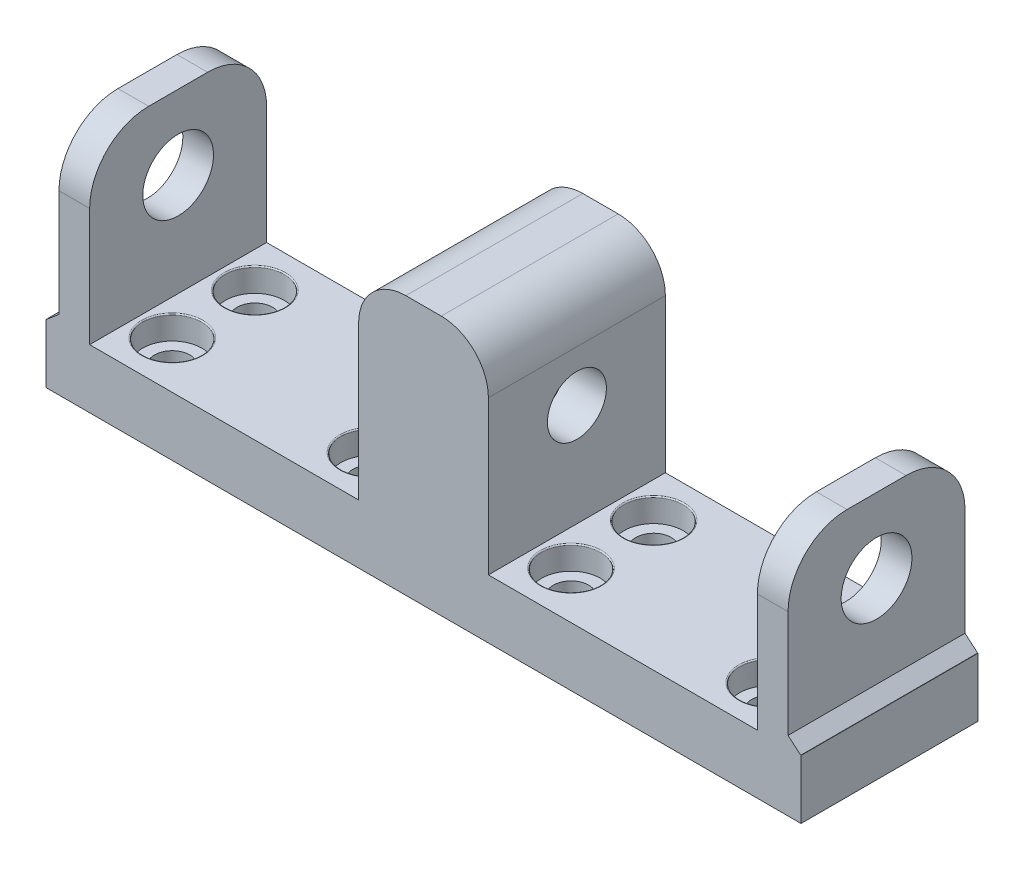
SolidWorks part; units mm, degrees
ref_plane "Alzado" through (0, 0, 0) normal (0, 0, 1) x (1, 0, 0)
ref_plane "Planta" through (0, 0, 0) normal (0, 1, 0) x (1, 0, 0)
ref_plane "Vista lateral" through (0, 0, 0) normal (1, 0, 0) x (0, 0, -1)
sketch "Croquis1" plane through (0, 0, 0) normal (0, 0, 1) x (1, 0, 0)
  line L0 (0, 11) -> (0, -11) construction
  line L1 (-1.5, 11) -> (1.5, 11)
  line L2 (-5.5, 7) -> (-5.5, -6)
  line L3 (-5.5, -11) -> (5.5, -11)
  line L4 (5.5, 7) -> (5.5, -6)
  line L5 (-5.5, 11) -> (5.5, -11) construction
  line L6 (-5.5, -11) -> (5.5, 11) construction
  line L7 (-5.5, -11) -> (-11.5, -11)
  line L9 (-5.5, -6) -> (-11.5, -6)
  line L10 (-11.5, -11) -> (-11.5, -6)
  line L11 (5.5, -6) -> (11.5, -6)
  line L12 (11.5, -11) -> (11.5, -6)
  line L13 (5.5, -11) -> (11.5, -11)
  arc A0 (5.5, 7) -> (1.5, 11) centre (1.5, 7) ccw
  arc A1 (-5.5, 7) -> (-1.5, 11) centre (-1.5, 7) cw
  point P0 (0, 0)
  dimension "D1" = 4
  dimension "D2" = 6
  dimension "D3" = 5
  dimension "D4" = 11
  dimension "D5" = 18
extrude "Saliente-Extruir1" add sketch "Croquis1" against normal blind 15
sketch "Croquis2" plane through (5.5, 0, 0) normal (1, 0, 0) x (0, 0, -1)
  line L0 (7.5, 11) -> (7.5, -6) construction
  line L1 (15, 11) -> (0, 11) construction
  line L2 (15, -6) -> (0, -6) construction
  line L3 (15, -11) -> (0, -11) construction
  circle A0 centre (7.5, 2.7) radius 2.5
  dimension "D2" = 5
  dimension "D1" = 13.7
extrude "Cortar-Extruir1" cut sketch "Croquis2" against normal blind 3.5
sketch "Croquis3" plane through (-5.5, 0, 0) normal (-1, 0, 0) x (0, 0, 1)
  line L0 (-7.5, 11) -> (-7.5, -6) construction
  line L1 (-15, 11) -> (0, 11) construction
  line L2 (-15, -6) -> (0, -6) construction
  line L3 (-15, -11) -> (0, -11) construction
  circle A0 centre (-7.5, 2.7) radius 2.5
  dimension "D2" = 5
  dimension "D1" = 13.7
extrude "Cortar-Extruir2" cut sketch "Croquis3" against normal blind 3.5
sketch "Croquis4" plane through (0, -6, 0) normal (0, 1, 0) x (1, 0, 0)
  line L0 (0, 15) -> (0, 0) construction
  line L1 (1.5, 15) -> (-1.5, 15) construction
  line L2 (-8.5, 15) -> (-8.5, 0) construction
  line L3 (-5.5, 15) -> (-11.5, 15) construction
  line L4 (-5.5, 0) -> (-11.5, 0) construction
  circle A0 centre (-8.5, 11) radius 2.5
  circle A1 centre (-8.5, 4) radius 2.5
  circle A2 centre (8.5, 4) radius 2.5
  circle A3 centre (8.5, 11) radius 2.5
  dimension "D1" = 5
  dimension "D2" = 4
  dimension "D3" = 4
extrude "Cortar-Extruir3" cut sketch "Croquis4" against normal blind 2
fillet "Redondeo1" radius 0.1 4 edges at (11, -6, -4) (11, -6, -11) (-11, -6, -4) (-11, -6, -11)
sketch "Croquis5" plane through (0, -6, 0) normal (0, 1, 0) x (1, 0, 0)
  line L0 (-8.5, 15) -> (-8.5, 0) construction
  line L1 (-5.5, 15) -> (-11.5, 15) construction
  line L2 (-5.5, 0) -> (-11.5, 0) construction
  line L3 (0, 15) -> (0, 0) construction
  line L4 (1.5, 15) -> (-1.5, 15) construction
  line L5 (1.5, 0) -> (-1.5, 0) construction
  circle A0 centre (-8.5, 11) radius 1.5
  circle A1 centre (-8.5, 4) radius 1.5
  circle A2 centre (-8.5, 11) radius 2.6 construction
  circle A3 centre (8.5, 4) radius 1.5
  circle A4 centre (8.5, 11) radius 1.5
  dimension "D1" = 3
extrude "Cortar-Extruir4" cut sketch "Croquis5" against normal through all
sketch "Croquis6" plane through (-11.5, 0, 0) normal (-1, 0, 0) x (0, 0, 1)
  line L1 (-15, -6) -> (0, -6)
  line L2 (-15, -6) -> (-15, -11)
  line L3 (-15, -11) -> (0, -11)
  line L4 (0, -6) -> (0, -11)
extrude "Saliente-Extruir2" add sketch "Croquis6" along normal blind 20.5
sketch "Croquis7" plane through (11.5, 0, 0) normal (1, 0, 0) x (0, 0, -1)
  line L1 (0, -6) -> (15, -6)
  line L2 (0, -6) -> (0, -11)
  line L3 (0, -11) -> (15, -11)
  line L4 (15, -6) -> (15, -11)
extrude "Saliente-Extruir3" add sketch "Croquis7" along normal blind 20.5
sketch "Croquis8" plane through (0, -6, 0) normal (0, 1, 0) x (1, 0, 0)
  line L0 (-5.5, 15) -> (-32, 15) construction
  line L1 (-30.9, 15) -> (-28.3, 15)
  line L2 (-30.9, 15) -> (-30.9, 0)
  line L3 (-30.9, 0) -> (-28.3, 0)
  line L4 (-28.3, 15) -> (-28.3, 0)
  line L5 (-5.5, 0) -> (-32, 0) construction
  line L6 (0, 15) -> (0, 0) construction
  line L7 (1.5, 15) -> (-1.5, 15) construction
  line L8 (30.9, 0) -> (28.3, 0)
  line L9 (28.3, 15) -> (28.3, 0)
  line L10 (30.9, 15) -> (28.3, 15)
  line L11 (30.9, 15) -> (30.9, 0)
  line L12 (-32, 0) -> (-32, 15) construction
  dimension "D1" = 2.6
  dimension "D2" = 1.1
extrude "Saliente-Extruir4" add sketch "Croquis8" along normal blind 15
fillet "Redondeo4" radius 5 2 edges at (-29.6, 9, -15) (-29.6, 9, 0)
fillet "Redondeo5" radius 5 2 edges at (29.6, 9, -15) (29.6, 9, 0)
ref_plane "Plano12" through (0, 0, -7.5) normal (0, 0, 1) x (1, 0, 0)
sketch "Croquis17" plane through (0, 0, -7.5) normal (0, 0, 1) x (1, 0, 0)
  line L0 (30.9, -5.0818) -> (31.9724, -6)
  line L1 (30.9, 4) -> (30.9, -6) construction
  line L3 (32, -6) -> (30.9, -6) construction
  point P2 (0, 0)
  point P3 (0, 0)
  point P4 (0, 0)
  point P7 (0, 0)
  point P8 (0, 0)
  point P9 (0, 0)
  point P10 (0, 0)
  point P11 (32.0303, -5.6488)
  point P12 (0, 0)
  point P13 (31.7027, -5.9048)
  point P14 (0, 0)
  point P17 (31.8333, -6)
  point P18 (0, 0)
  point P19 (0, 0)
  point P20 (0, 0)
  point P21 (0, 0)
  point P22 (31.9724, -6)
rib "Nervio1" sketch "Croquis17" sketch "Croquis17" thickness 15 extrusion direction parallel to sketch draft on no parameters "D1"=15
sketch "Croquis22" plane through (0, 0, -7.5) normal (0, 0, 1) x (1, 0, 0)
  line L0 (-31.9933, -6) -> (-30.9, -5.0818)
  line L1 (-30.9, -6) -> (-32, -6) construction
  line L2 (-30.9, 9) -> (-30.9, 4) construction
  line L4 (-30.9, 4) -> (-30.9, -6) construction
  point P1 (-31.9933, -6)
  point P2 (-30.9, -5.0743)
rib "Nervio2" sketch "Croquis22" sketch "Croquis22" thickness 15 extrusion direction parallel to sketch draft on no parameters "D1"=15
sketch "Croquis23" plane through (30.9, 0, 0) normal (1, 0, 0) x (0, 0, -1)
  line L0 (7.5, 9) -> (7.5, -5.0818) construction
  line L1 (5, 9) -> (10, 9) construction
  line L2 (0, -5.0818) -> (15, -5.0818) construction
  line L3 (0, -11) -> (15, -11) construction
  circle A0 centre (7.5, 2.7) radius 3
  dimension "D1" = 6
  dimension "D2" = 13.7
extrude "Cortar-Extruir5" cut sketch "Croquis23" against normal blind 7
sketch "Croquis24" plane through (-30.9, 0, 0) normal (-1, 0, 0) x (0, 0, 1)
  line L0 (-7.5, 9) -> (-7.5, -5.0818) construction
  line L1 (-10, 9) -> (-5, 9) construction
  line L2 (-15, -5.0818) -> (0, -5.0818) construction
  line L3 (-15, -11) -> (0, -11) construction
  circle A0 centre (-7.5, 2.7) radius 3
  dimension "D1" = 6
  dimension "D2" = 13.7
extrude "Cortar-Extruir6" cut sketch "Croquis24" against normal blind 7
sketch "Croquis27" plane through (0, -6, 0) normal (0, 1, 0) x (1, 0, 0)
  line L0 (-25.3, 15) -> (-25.3, 0) construction
  line L1 (-5.5, 15) -> (-28.3, 15) construction
  line L2 (-5.5, 0) -> (-28.3, 0) construction
  line L3 (-28.3, 0) -> (-28.3, 15) construction
  circle A0 centre (-25.3, 11) radius 1.5
  circle A1 centre (-25.3, 4) radius 1.5
  circle A2 centre (-25.3, 11) radius 2.5
  circle A3 centre (-25.3, 4) radius 2.5
  point P12 (0, 0)
  point P13 (0, 0)
  point P14 (0, 0)
  point P15 (0, 0)
  dimension "D1" = 3
  dimension "D2" = 5
  dimension "D3" = 4
  dimension "D4" = 4
  dimension "D5" = 3
extrude "Cortar-Extruir8" cut sketch "Croquis27" against normal through all contours A0 | A1
sketch "Croquis29" plane through (0, -6, 0) normal (0, 1, 0) x (1, 0, 0)
  circle A0 centre (-25.3, 11) radius 2.5
  circle A1 centre (-25.3, 4) radius 2.5
  dimension "D1" = 5
extrude "Cortar-Extruir9" cut sketch "Croquis29" against normal blind 2
fillet "Redondeo6" radius 0.1 2 edges at (-27.8, -6, -4) (-27.8, -6, -11)
sketch "Croquis30" plane through (0, -6, 0) normal (0, 1, 0) x (1, 0, 0)
  line L0 (25.3, 15) -> (25.3, 0) construction
  line L1 (28.3, 15) -> (5.5, 15) construction
  line L2 (28.3, 0) -> (5.5, 0) construction
  line L3 (28.3, 15) -> (28.3, 0) construction
  circle A0 centre (25.3, 11) radius 1.5
  circle A1 centre (25.3, 4) radius 1.5
  point P12 (0, 0)
  point P13 (0, 0)
  dimension "D2" = 3
  dimension "D1" = 3
  dimension "D3" = 4
  dimension "D4" = 4
extrude "Cortar-Extruir10" cut sketch "Croquis30" against normal through all
sketch "Croquis32" plane through (0, -6, 0) normal (0, 1, 0) x (1, 0, 0)
  circle A0 centre (25.3, 11) radius 2.5
  circle A1 centre (25.3, 4) radius 2.5
  dimension "D1" = 5
extrude "Cortar-Extruir11" cut sketch "Croquis32" against normal blind 2
fillet "Redondeo7" radius 0.1 2 edges at (22.8, -6, -4) (22.8, -6, -11)
